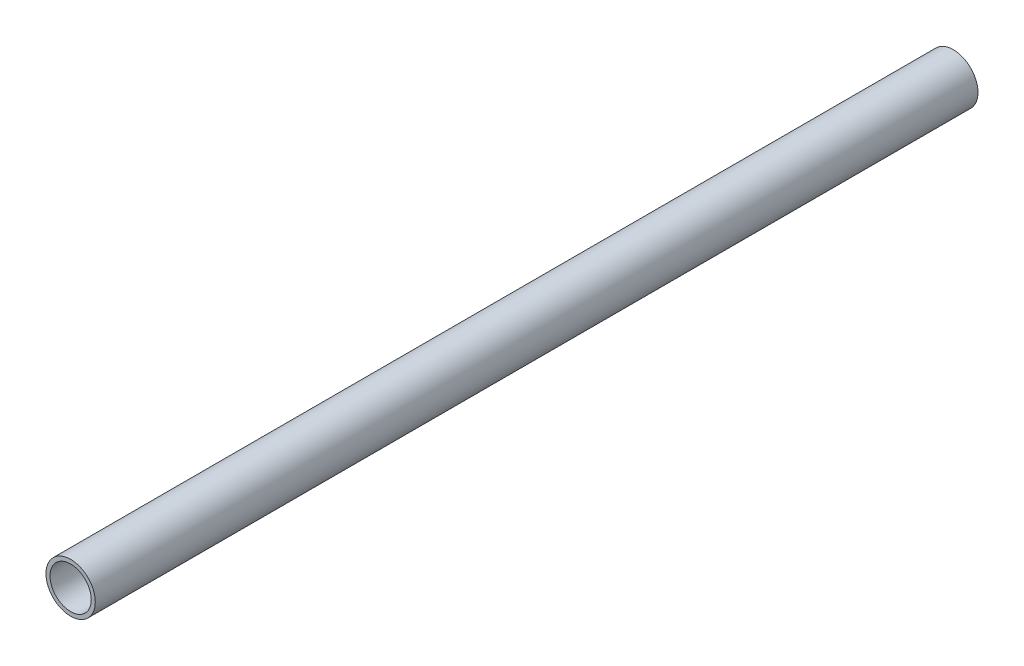
SolidWorks part; units mm, degrees
material "PVC Rigid"
ref_plane "Front Plane" through (0, 0, 0) normal (0, 0, 1) x (1, 0, 0)
ref_plane "Top Plane" through (0, 0, 0) normal (0, 1, 0) x (1, 0, 0)
ref_plane "Right Plane" through (0, 0, 0) normal (1, 0, 0) x (0, 0, -1)
sketch "Sketch1" plane through (0, 0, 0) normal (0, 0, 1) x (1, 0, 0)
  circle A0 centre (0, 0) radius 20.193
  circle A1 centre (0, 0) radius 24.13
  dimension "D1" = 48.26
  dimension "D2" = 40.386
extrude "Boss-Extrude1" add sketch "Sketch1" along normal blind 863.6
ref_axis "Axis1" through (0, 0, 863.6) along (0, 0, -1)
